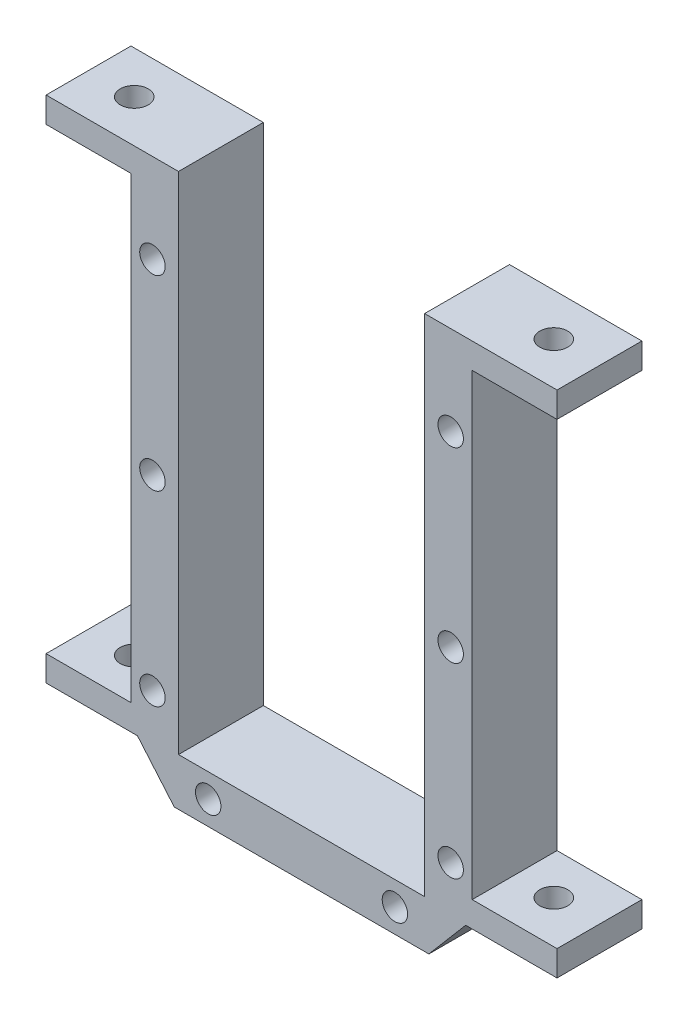
SolidWorks part; units mm, degrees
ref_plane "Front Plane" through (0, 0, 0) normal (0, 0, 1) x (1, 0, 0)
ref_plane "Top Plane" through (0, 0, 0) normal (0, 1, 0) x (1, 0, 0)
ref_plane "Right Plane" through (0, 0, 0) normal (1, 0, 0) x (0, 0, -1)
sketch "Sketch1" plane through (0, 0, 0) normal (0, 0, 1) x (1, 0, 0)
  line L1 (-20.1, 32.55) -> (20.1, 32.55)
  line L2 (-20.1, 32.55) -> (-20.1, -32.55)
  line L3 (-20.1, -32.55) -> (20.1, -32.55)
  line L4 (20.1, 32.55) -> (20.1, -32.55)
  point P0 (0, 0)
  dimension "D1" = 40.2
  dimension "D2" = 65.1
extrude "Boss-Extrude1" add sketch "Sketch1" along normal blind 10
sketch "Sketch2" plane through (0, 0, 10) normal (0, 0, 1) x (1, 0, 0)
  line L0 (0, 32.55) -> (0, -32.55) construction
  line L1 (20.1, 32.55) -> (-20.1, 32.55) construction
  line L2 (-20.1, -32.55) -> (20.1, -32.55) construction
  line L3 (-20.1, 0) -> (20.1, 0) construction
  line L4 (-20.1, 32.55) -> (-20.1, -32.55) construction
  line L5 (20.1, -32.55) -> (20.1, 32.55) construction
  line L6 (-20.1, -27.45) -> (20.1, -27.45) construction
  line L7 (15, -32.55) -> (19.335, -27.45)
  line L8 (19.335, -27.45) -> (15, -32.55) construction
  line L9 (19.335, -27.45) -> (20.1, -27.45)
  line L22 (20.1, -27.45) -> (20.1, -32.55)
  line L23 (20.1, -32.55) -> (15, -32.55)
  line L24 (-20.1, -27.45) -> (-20.1, -32.55)
  line L25 (-19.335, -27.45) -> (-20.1, -27.45)
  line L26 (-15, -32.55) -> (-19.335, -27.45)
  line L27 (-20.1, -32.55) -> (-15, -32.55)
  point P12 (0, -27.45)
  point P13 (-19.335, -27.45)
  point P17 (0, -27.45)
  point P18 (19.335, -27.45)
  dimension "D1" = 60
extrude "Cut-Extrude1" cut sketch "Sketch2" against normal blind 10
sketch "Sketch4" plane through (0, 0, 10) normal (0, 0, 1) x (1, 0, 0)
  line L0 (0, 32.55) -> (0, -32.55) construction
  line L1 (20.1, 32.55) -> (-20.1, 32.55) construction
  line L2 (-15, -32.55) -> (15, -32.55) construction
  line L3 (-20.1, 2.55) -> (20.1, 2.55) construction
  line L4 (-20.1, 32.55) -> (-20.1, -27.45) construction
  line L5 (20.1, -27.45) -> (20.1, 32.55) construction
  line L6 (14.5, -26.95) -> (-14.5, -26.95) construction
  line L7 (-14.5, -26.95) -> (-14.5, 32.55) construction
  line L8 (14.5, -26.95) -> (14.5, 32.55) construction
  line L9 (-14.5, 32.55) -> (-14.5, -26.95)
  line L10 (-14.5, -26.95) -> (14.5, -26.95)
  line L11 (14.5, -26.95) -> (14.5, 32.55)
  line L12 (14.5, 32.55) -> (-14.5, 32.55)
  point P12 (0, -26.95)
  point P16 (0, -26.95)
  dimension "D1" = 5.6
  dimension "D2" = 29
extrude "Cut-Extrude2" cut sketch "Sketch4" against normal blind 10
sketch "Sketch5" plane through (0, 0, 10) normal (0, 0, 1) x (1, 0, 0)
  line L0 (-14.5, 32.55) -> (14.5, 32.55) construction
  line L1 (0, 32.55) -> (0, -32.55) construction
  line L2 (-15, -32.55) -> (15, -32.55) construction
  line L3 (-15, -32.55) -> (15, -32.55) construction
  line L6 (-20.1, 32.55) -> (-20.1, -27.45) construction
  circle A0 centre (-17.5696, 22.05) radius 1.5
  circle A1 centre (-17.5696, 0.05) radius 1.5
  circle A2 centre (-17.5696, -21.95) radius 1.5
  circle A3 centre (-11, -29.75) radius 1.5
  circle A4 centre (11, -29.75) radius 1.5
  circle A5 centre (17.5696, -21.95) radius 1.5
  circle A6 centre (17.5696, 0.05) radius 1.5
  circle A7 centre (17.5696, 22.05) radius 1.5
  point P8 (-17.5696, 22.05)
  point P9 (-17.5696, 0.05)
  point P10 (-17.5696, -21.95)
  point P11 (-11, -29.75)
  point P22 (11, -29.75)
  point P25 (17.5696, -21.95)
  point P28 (17.5696, 0.05)
  point P31 (17.5696, 22.05)
  dimension "D6" = 3
  dimension "D7" = 3
  dimension "D8" = 3
  dimension "D9" = 3
  dimension "D1" = 10.6
  dimension "D2" = 32.6
  dimension "D3" = 54.6
  dimension "D4" = 2.8
  dimension "D5" = 9.1
extrude "Cut-Extrude3" cut sketch "Sketch5" against normal blind 10
sketch "Sketch6" plane through (0, 0, 10) normal (0, 0, 1) x (1, 0, 0)
  line L0 (-14.5, 32.55) -> (14.5, 32.55) construction
  line L1 (0, 32.55) -> (0, -32.55) construction
  line L2 (-15, -32.55) -> (15, -32.55) construction
  line L3 (-20.1, 2.55) -> (20.1, 2.55) construction
  line L4 (-20.1, 32.55) -> (-20.1, -27.45) construction
  line L5 (20.1, -27.45) -> (20.1, 32.55) construction
  point P14 (0, 0)
  point P17 (0, 0)
  point P19 (0, 0)
  point P23 (0, 0)
sketch "Sketch7" plane through (20.1, 0, 0) normal (1, 0, 0) x (0, 0, -1)
  line L0 (0, 2.55) -> (-10, 2.55) construction
  line L1 (-10, 32.55) -> (-10, -32.55) construction
  line L2 (0, -27.45) -> (0, 32.55) construction
  line L3 (0, 29.55) -> (-10, 29.55)
  line L4 (-10, 29.55) -> (-10, 32.55)
  line L5 (-10, 32.55) -> (0, 32.55)
  line L6 (0, 32.55) -> (0, 29.55)
  line L7 (-10, -27.45) -> (-10, 32.55) construction
  line L8 (-10, -27.45) -> (0, -27.45)
  line L9 (-10, -24.45) -> (-10, -27.45)
  line L10 (0, -24.45) -> (-10, -24.45)
  line L11 (0, -27.45) -> (0, -24.45)
  point P5 (0, 29.55)
  dimension "D1" = 3
extrude "Boss-Extrude2" add sketch "Sketch7" along normal blind 10
sketch "Sketch8" plane through (-20.1, 0, 0) normal (-1, 0, 0) x (0, 0, 1)
  line L0 (0, 2.55) -> (10, 2.55) construction
  line L1 (0, 32.55) -> (0, -27.45) construction
  line L2 (10, 32.55) -> (10, -32.55) construction
  line L3 (0, 29.55) -> (10, 29.55)
  line L4 (10, 29.55) -> (10, 32.55)
  line L5 (10, 32.55) -> (0, 32.55)
  line L6 (0, 32.55) -> (0, 29.55)
  line L7 (10, -27.45) -> (0, -27.45)
  line L8 (10, -24.45) -> (10, -27.45)
  line L9 (0, -24.45) -> (10, -24.45)
  line L10 (0, -27.45) -> (0, -24.45)
  point P6 (0, 29.55)
  dimension "D1" = 3
extrude "Boss-Extrude3" add sketch "Sketch8" along normal blind 10
sketch "Sketch9" plane through (0, -27.45, 0) normal (0, -1, 0) x (-1, 0, 0)
  line L0 (24.7175, -10) -> (24.7175, 0) construction
  line L1 (19.335, -10) -> (30.1, -10) construction
  line L2 (19.335, 0) -> (30.1, 0) construction
  line L3 (30.1, -5) -> (19.335, -5) construction
  line L4 (30.1, 0) -> (30.1, -10) construction
  line L5 (19.335, 0) -> (19.335, -10) construction
  circle A0 centre (24.7175, -5) radius 1.65
  dimension "D1" = 3.3
extrude "Cut-Extrude4" cut sketch "Sketch9" against normal through all
sketch "Sketch10" plane through (0, -27.45, 0) normal (0, -1, 0) x (-1, 0, 0)
  line L0 (-24.7175, -10) -> (-24.7175, 0) construction
  line L1 (-30.1, -10) -> (-19.335, -10) construction
  line L2 (-30.1, 0) -> (-19.335, 0) construction
  line L3 (-19.335, -5) -> (-30.1, -5) construction
  line L4 (-19.335, 0) -> (-19.335, -10) construction
  line L5 (-30.1, -10) -> (-30.1, 0) construction
  circle A0 centre (-24.7175, -5) radius 1.65
  dimension "D1" = 3.3
extrude "Cut-Extrude5" cut sketch "Sketch10" against normal through all
